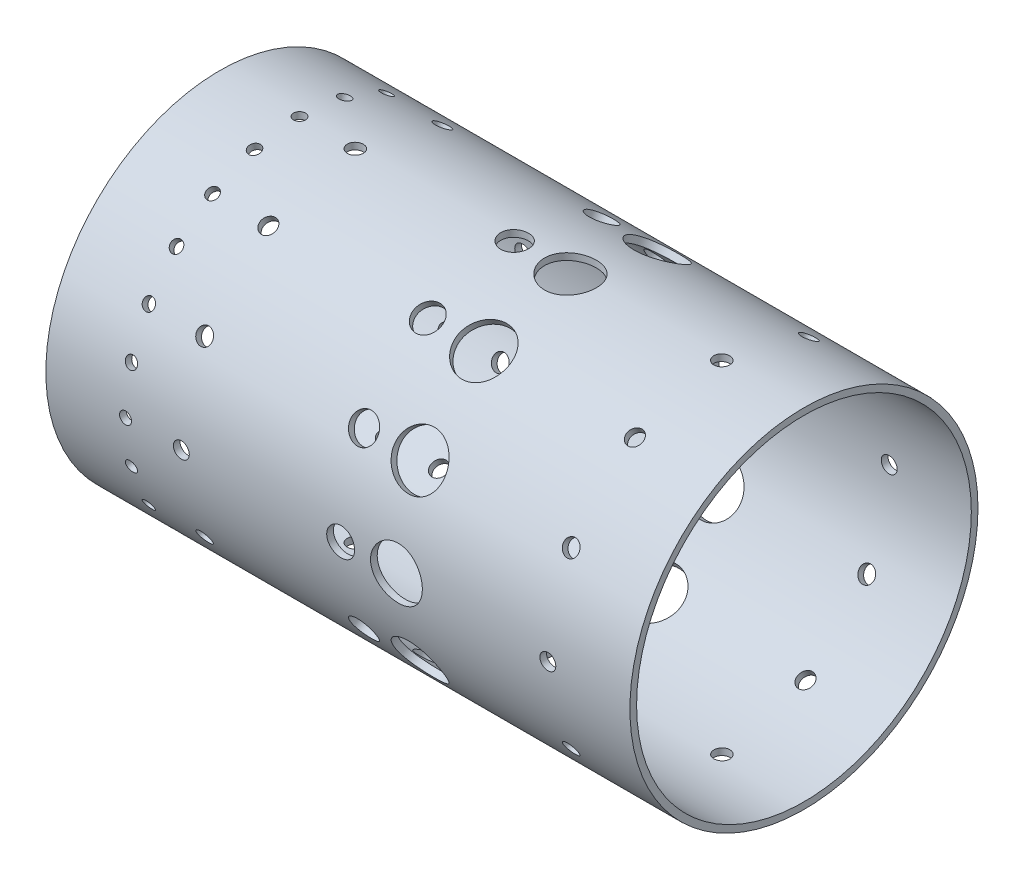
SolidWorks part; units mm, degrees
ref_plane "Front Plane" through (0, 0, 0) normal (0, 0, 1) x (1, 0, 0)
ref_plane "Top Plane" through (0, 0, 0) normal (0, 1, 0) x (1, 0, 0)
ref_plane "Right Plane" through (0, 0, 0) normal (1, 0, 0) x (0, 0, -1)
sketch "Sketch1" plane through (0, 0, 0) normal (1, 0, 0) x (0, 0, -1)
  circle A0 centre (0, 0) radius 21.0058
  circle A1 centre (0, 0) radius 21.844
  dimension "D1" = 43.688
  dimension "D2" = 0.8382
extrude "Boss-Extrude1" add sketch "Sketch1" along normal blind 73.3044
sketch "Sketch3" plane through (0, 0, 0) normal (0, 1, 0) x (1, 0, 0)
  line L0 (0, 0) -> (79.3536, 0) construction
sketch "Sketch4" plane through (0, 0, 0) normal (0, 1, 0) x (1, 0, 0)
  line L0 (0, 0) -> (79.3536, 0) construction
  circle A0 centre (10, 0) radius 0.75
  dimension "D2" = 1.5
  dimension "D1" = 10
extrude "Cut-Extrude1" cut sketch "Sketch4" against normal through all
pattern_circular "CirPattern1" count 24 over 360 about axis through (0, 0, 0) along (1, 0, 0) of "Cut-Extrude1"
sketch "Sketch5" plane through (0, 0, 0) normal (0, 1, 0) x (1, 0, 0)
  line L0 (0, 0) -> (79.3536, 0) construction
  line L1 (0, 21.844) -> (0, -21.844) construction
  circle A0 centre (17, 0) radius 1
  dimension "D2" = 2
  dimension "D1" = 17
extrude "Cut-Extrude3" cut sketch "Sketch5" against normal through all
pattern_circular "CirPattern2" count 12 over 360 about axis through (0, 0, 0) along (1, 0, 0) of "Cut-Extrude3"
sketch "Sketch6" plane through (0, 0, 0) normal (0, 1, 0) x (1, 0, 0)
  line L0 (0, 0) -> (79.3536, 0) construction
  line L1 (0, 21.844) -> (0, -21.844) construction
  circle A0 centre (37, 0) radius 1.75
  dimension "D2" = 3.5
  dimension "D1" = 37
extrude "Cut-Extrude4" cut sketch "Sketch6" against normal through all
pattern_circular "CirPattern3" count 12 over 360 about axis through (0, 0, 0) along (1, 0, 0) of "Cut-Extrude4"
sketch "Sketch7" plane through (0, 0, 0) normal (0, 1, 0) x (1, 0, 0)
  line L0 (0, 0) -> (79.3536, 0) construction
  circle A0 centre (44, 0) radius 3.25
  dimension "D2" = 6.5
  dimension "D1" = 44
extrude "Cut-Extrude5" cut sketch "Sketch7" against normal through all
pattern_circular "CirPattern5" count 12 over 360 about axis through (0, 0, 0) along (1, 0, 0) of "Cut-Extrude5" reverse direction yes
sketch "Sketch8" plane through (0, 0, 0) normal (0, 0, 1) x (1, 0, 0)
  line L0 (0, 0) -> (79.3536, 0) construction
  circle A0 centre (63, 0) radius 1
  dimension "D1" = 2
  dimension "D2" = 63
extrude "Cut-Extrude6" cut sketch "Sketch8" against normal through all
pattern_circular "CirPattern6" count 12 over 360 about axis through (0, 0, 0) along (1, 0, 0) of "Cut-Extrude6" reverse direction yes
